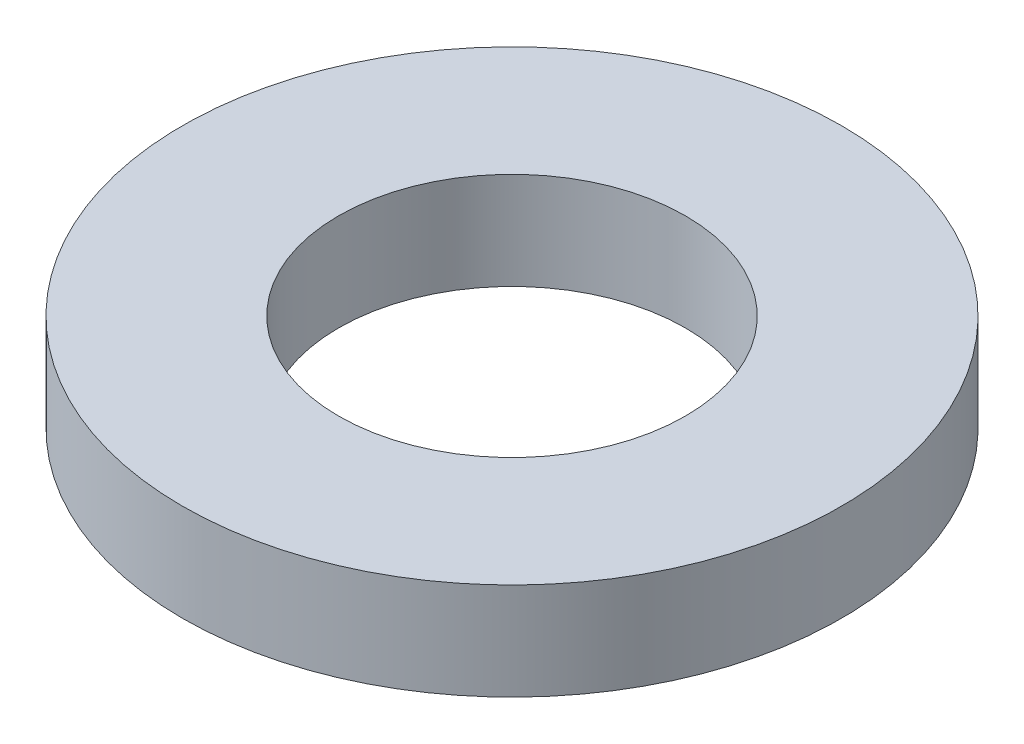
SolidWorks part; units mm, degrees
ref_plane "Front Plane" through (0, 0, 0) normal (0, 0, 1) x (1, 0, 0)
ref_plane "Top Plane" through (0, 0, 0) normal (0, 1, 0) x (1, 0, 0)
ref_plane "Right Plane" through (0, 0, 0) normal (1, 0, 0) x (0, 0, -1)
sketch "Sketch1" plane through (0, 0, 0) normal (0, 1, 0) x (1, 0, 0)
  circle A0 centre (0, 0) radius 95
  dimension "FLANGE_OD" = 190
extrude "Boss-Extrude1" add sketch "Sketch1" along normal blind 28
sketch "Sketch2" plane through (0, 0, 0) normal (0, 1, 0) x (1, 0, 0)
  circle A0 centre (0, 0) radius 50
  dimension "BORE_D" = 100
extrude "Cut-Extrude1" cut sketch "Sketch2" along normal through all
sketch "Sketch3" plane through (0, 28, 0) normal (0, 1, 0) x (1, 0, 0)
  circle A0 centre (0, 0) radius 29.522 construction
  circle A1 centre (-29.522, 0) radius 2.6711
  dimension "BOLT_D" = 5.3423
  dimension "BOLT_PCD" = 59.044
extrude "Cut-Extrude2" cut sketch "Sketch3" against normal blind 17.2043 rebuild error yes
pattern_circular "CirPattern1" count 3 over 360 rebuild error yes
